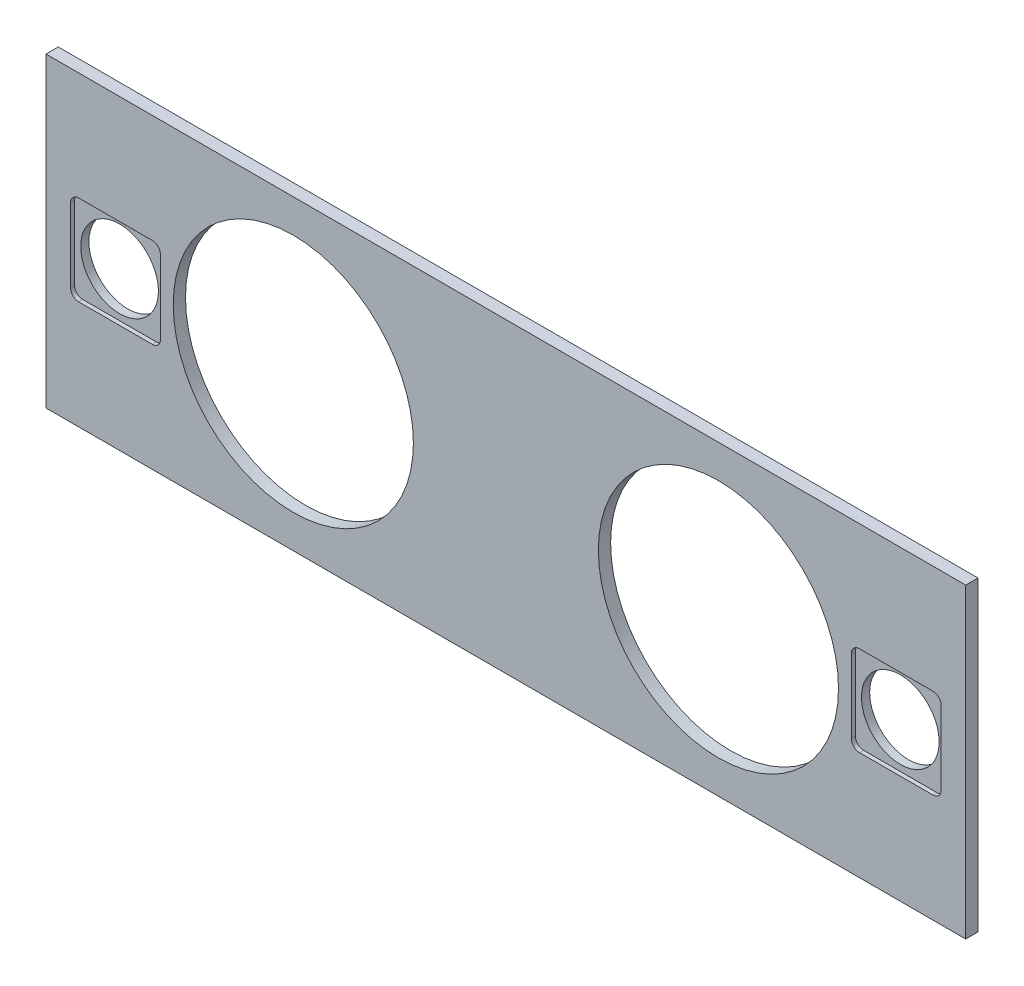
SolidWorks part; units mm, degrees
material "Pine"
ref_plane "Front Plane" through (0, 0, 0) normal (0, 0, 1) x (1, 0, 0)
ref_plane "Top Plane" through (0, 0, 0) normal (0, 1, 0) x (1, 0, 0)
ref_plane "Right Plane" through (0, 0, 0) normal (1, 0, 0) x (0, 0, -1)
sketch "Sketch1" plane through (0, 0, 0) normal (0, 0, 1) x (1, 0, 0)
  line L5 (450, 424.6951) -> (450, -112.2601) construction
  line L6 (0, 0) -> (900, 0)
  line L10 (0, 0) -> (0, 300)
  line L11 (0, 300) -> (900, 300)
  line L12 (900, 0) -> (900, 300)
  circle A0 centre (242, 150) radius 117.5
  circle A2 centre (658, 150) radius 117.5
  circle A3 centre (68, 150) radius 38
  circle A4 centre (832, 150) radius 38
  dimension "D1" = 235
  dimension "D4" = 242
  dimension "D5" = 150
  dimension "D6" = 68
  dimension "D7" = 150
  dimension "D8" = 76
  dimension "D2" = 900
  dimension "D3" = 300
extrude "Boss-Extrude1" add sketch "Sketch1" along normal blind 12 contours A2 | A0 | L10 L11 L12 L6 | A3 | A4 region at (658, 150, 0)
sketch "Sketch4" plane through (0, 0, 12) normal (0, 0, 1) x (1, 0, 0)
  line L1 (32, 194) -> (104, 194)
  line L2 (24, 186) -> (24, 114)
  line L3 (32, 106) -> (104, 106)
  line L4 (112, 186) -> (112, 114)
  line L5 (0, 0) -> (0, 300) construction
  line L6 (0, 300) -> (900, 300) construction
  line L7 (450, -84.0445) -> (450, 394.2312) construction
  line L8 (868, 106) -> (796, 106)
  line L9 (788, 186) -> (788, 114)
  line L10 (868, 194) -> (796, 194)
  line L11 (876, 186) -> (876, 114)
  arc A0 (104, 194) -> (112, 186) centre (104, 186) cw
  arc A1 (104, 106) -> (112, 114) centre (104, 114) ccw
  arc A2 (24, 114) -> (32, 106) centre (32, 114) ccw
  arc A3 (24, 186) -> (32, 194) centre (32, 186) cw
  arc A4 (796, 106) -> (788, 114) centre (796, 114) cw
  arc A5 (796, 194) -> (788, 186) centre (796, 186) ccw
  arc A6 (876, 114) -> (868, 106) centre (868, 114) cw
  arc A7 (876, 186) -> (868, 194) centre (868, 186) ccw
  point P16 (67.7235, 149.5451)
  dimension "D1" = 8
  dimension "D2" = 88
  dimension "D3" = 88
  dimension "D4" = 24
  dimension "D5" = 106
extrude "Cut-Extrude1" cut sketch "Sketch4" against normal blind 4 contours L2 A2 L3 A1 L4 A0 L1 A3 | L8 A4 L9 A5 L10 A7 L11 A6
